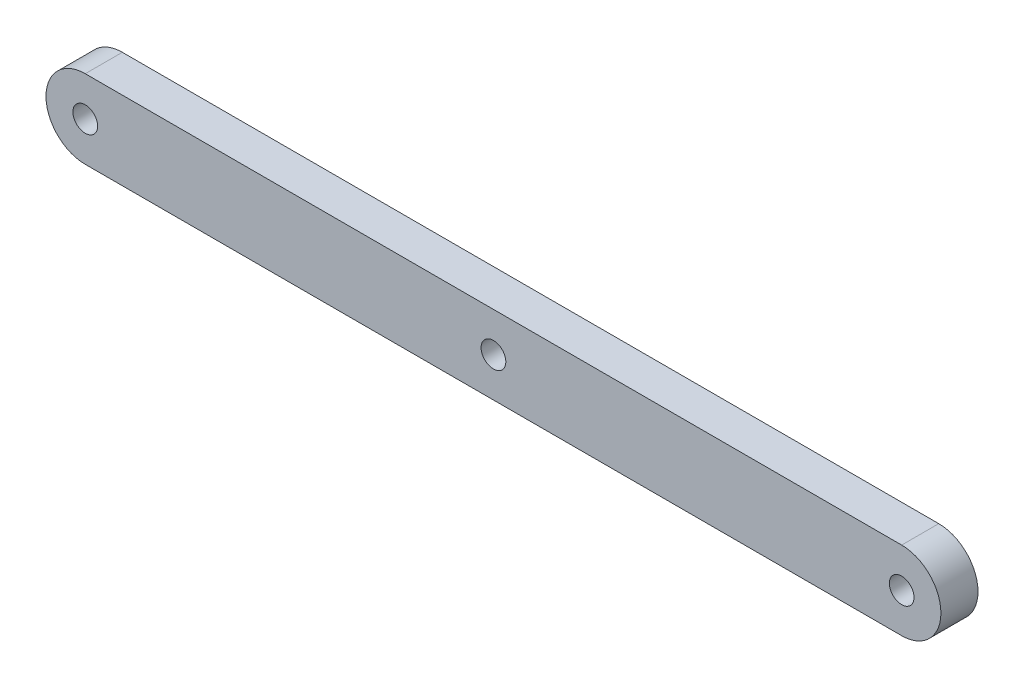
SolidWorks part; units mm, degrees
ref_plane "Front Plane" through (0, 0, 0) normal (0, 0, 1) x (1, 0, 0)
ref_plane "Top Plane" through (0, 0, 0) normal (0, 1, 0) x (1, 0, 0)
ref_plane "Right Plane" through (0, 0, 0) normal (1, 0, 0) x (0, 0, -1)
sketch "Sketch2" plane through (0, 0, 0) normal (0, 0, 1) x (1, 0, 0)
  line L0 (0, 0) -> (66.04, 0)
  dimension "D1" = 66.04
extrude "Extrude-Thin1" add sketch "Sketch2" along normal blind 3 thin thin type mid plane wall 6.35
sketch "Sketch3" plane through (0, 0, 3) normal (0, 0, 1) x (1, 0, 0)
  line L0 (66.04, 3.175) -> (66.04, -3.175) construction
  line L1 (0, 3.175) -> (66.04, 3.175) construction
  circle A0 centre (0, 0) radius 3.175
  circle A1 centre (66.04, 0) radius 3.175
  circle A2 centre (0, 0) radius 1
  circle A3 centre (66.04, 0) radius 1
  circle A4 centre (33.02, 0) radius 1
  point P16 (33.02, 3.175)
  line M3 (66.04, -3.175) -> (66.04, 3.175)
  line M5 (0, 3.175) -> (0, -3.175)
  dimension "D1" = 2
extrude "Boss-Extrude1" add sketch "Sketch3" against normal through all
extrude "Cut-Extrude1" cut sketch "Sketch3<2>" against normal through all contours A2 M5 | A3 M3 | A4 region at (0.4244, 0, 3) region at (65.6156, 0, 3) region at (33.02, 0, 3)
sketch "Sketch3<2>" plane through (0, 0, 3) normal (0, 0, 1) x (1, 0, 0) same geometry as "Sketch3"
equation "\"member length\"= 1.3"
equation "\"member width\"= 1 / 4"
equation "\"member thickness\"= 3mm"
equation "\"D1@Sketch2\"=\"member length\"*2"
equation "\"D5@Extrude-Thin1\"=\"member width\""
equation "\"D1@Extrude-Thin1\"=\"member thickness\""
equation "\"hole size\"= 2mm"
equation "\"D1@Sketch3\"=\"hole size\""
